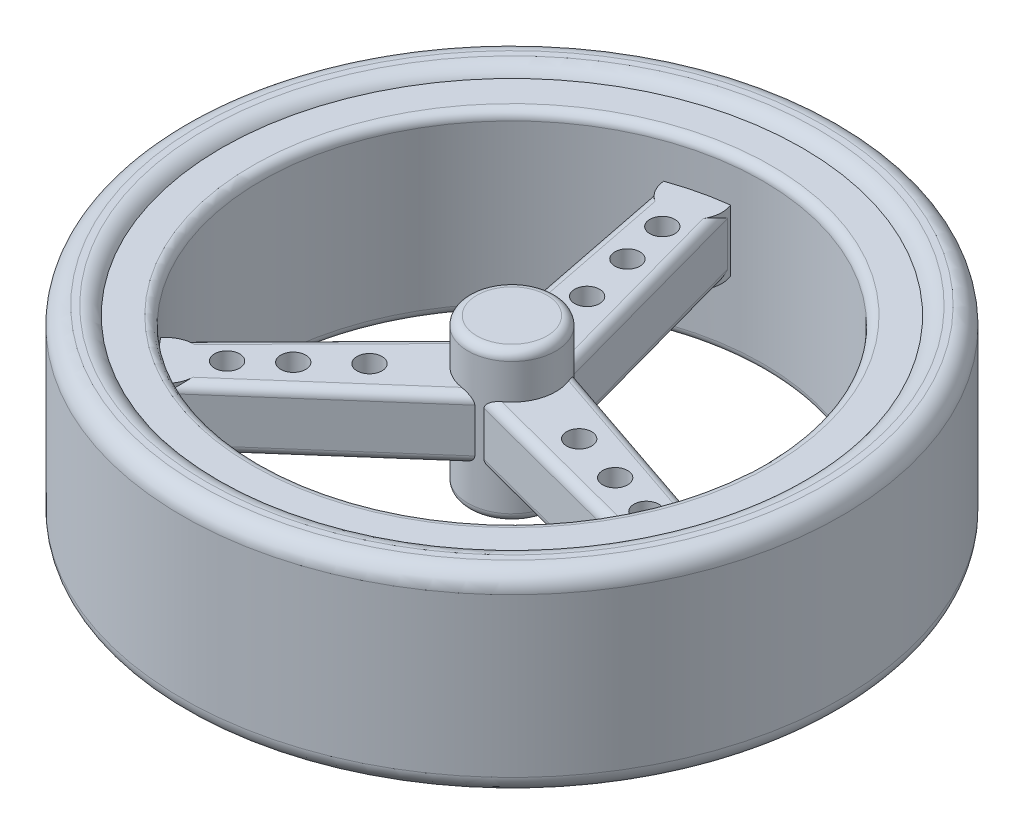
SolidWorks part; units mm, degrees
ref_plane "Front Plane" through (0, 0, 0) normal (0, 0, 1) x (1, 0, 0)
ref_plane "Top Plane" through (0, 0, 0) normal (0, 1, 0) x (1, 0, 0)
ref_plane "Right Plane" through (0, 0, 0) normal (1, 0, 0) x (0, 0, -1)
sketch "Sketch1" plane through (0, 0, 0) normal (0, 1, 0) x (1, 0, 0)
  circle A0 centre (0, 0) radius 5
  dimension "D1" = 10
extrude "Boss-Extrude1" add sketch "Sketch1" along normal blind 5
sketch "Sketch2" plane through (0, 5, 0) normal (0, 1, 0) x (1, 0, 0)
  line L0 (-3.2976, 27.8407) -> (3.3254, 3.7339)
  line L1 (0, 0) -> (0, 0.3854) construction
  line L2 (-1.1506, 4.8658) -> (-0.503, 2.1273) construction
  line L3 (-9.5211, 26.369) -> (-4.6455, 1.849)
  line L4 (27.5968, -4.939) -> (3.9241, 3.0986)
  line L5 (25.7595, -11.0646) -> (1.571, -4.7468)
  line L6 (-18.0757, -21.43) -> (0.7214, -4.9477)
  line L7 (-22.4619, -16.7761) -> (-4.8963, 1.0129)
  circle A0 centre (0, 0) radius 5 construction
  arc A1 (-4.6455, 1.849) -> (3.3254, 3.7339) centre (0, 0) cw
  arc A2 (-9.5211, 26.369) -> (-3.2976, 27.8407) centre (-6.4093, 27.1048) cw
  arc A3 (27.5968, -4.939) -> (25.7595, -11.0646) centre (26.6782, -8.0018) cw
  arc A4 (3.9241, 3.0986) -> (1.571, -4.7468) centre (0, 0) cw
  arc A5 (-18.0757, -21.43) -> (-22.4619, -16.7761) centre (-20.2688, -19.1031) cw
  arc A6 (0.7214, -4.9477) -> (-4.8963, 1.0129) centre (0, 0) cw
  point P24 (0, 0)
  dimension "D1" = 25
  dimension "D2" = 3
extrude "Boss-Extrude4" add sketch "Sketch2" along normal blind 7 separate body
sketch "Sketch3" plane through (0, 5, 0) normal (0, 1, 0) x (1, 0, 0)
  line L0 (-1.1506, 4.8658) -> (1.1506, -4.8658) construction
  arc A0 (3.3254, 3.7339) -> (-4.6455, 1.849) centre (0, 0) ccw construction
  circle A1 centre (0, 0) radius 5 construction
sketch "Sketch4" plane through (0, 5, 0) normal (0, 1, 0) x (1, 0, 0)
  circle A0 centre (0, 0) radius 5
  dimension "D1" = 10
extrude "Boss-Extrude5" add sketch "Sketch4" along normal blind 12
sketch "Sketch5" plane through (0, 17, 0) normal (0, 1, 0) x (1, 0, 0)
  circle A0 centre (0, 0) radius 28.5413
  circle A1 centre (0, 0) radius 33.0429
extrude "Boss-Extrude6" add sketch "Sketch5" against normal blind 20
fillet "Fillet1" radius 1 4 edges at (0, 17, 5) (0, 0, 5) (0, 17, 28.5413) (0, -3, 28.5413)
fillet "Fillet2" radius 1 10 edges at (-13.6791, 12, 7.8816) (-7.0833, 12, -14.109) (13.6652, 12, 7.9057) (15.7604, 12, 0.9202) (0.0139, 12, -15.7873) (0.0139, 5, -15.7873) (-7.0833, 5, -14.109) (-13.6791, 5, 7.8816) (-8.6771, 5, 13.1889) (13.6652, 5, 7.9057)
fillet "Fillet3" radius 1 1 edges at (-8.6771, 12, 13.1889)
sketch "Sketch9" plane through (0, -3, 0) normal (0, -1, 0) x (1, 0, 0)
  circle A0 centre (0, 0) radius 33.0429
  circle A1 centre (0, 0) radius 37.5
  dimension "D1" = 75
extrude "Boss-Extrude10" add sketch "Sketch9" against normal blind 21 and the other way blind 1
fillet "Fillet4" radius 2 2 edges at (0, -4, -33.0429) (0, 18, -33.0429)
fillet "Fillet5" radius 2 2 edges at (0, 18, -37.5) (0, -4, -37.5)
ref_plane "Plane1" through (0, 0, -37.5) normal (0, 0, -1) x (-1, 0, 0)
sketch "Sketch11" plane through (0, 0, -37.5) normal (0, 0, -1) x (-1, 0, 0)
  line L0 (2.1091, 14.5) -> (0, 14.5)
  line L1 (0, 16) -> (2.1091, 16)
  line L2 (0, 16) -> (0, -2)
  line L3 (0, -2) -> (2.1091, -2)
  line L4 (2.1091, 16) -> (2.1091, -2)
  line L5 (-37.5, 16) -> (37.5, 16) construction
  line L6 (37.5, -2) -> (-37.5, -2) construction
  line L7 (2.1091, 12.5) -> (0, 12.5)
  line L8 (2.1091, 10.5) -> (0, 10.5)
  line L9 (2.1091, 8.5) -> (0, 8.5)
  line L10 (2.1091, 6.5) -> (0, 6.5)
  line L11 (2.1091, 4.5) -> (0, 4.5)
  line L12 (2.1091, 2.5) -> (0, 2.5)
  line L13 (2.1091, 0.5) -> (0, 0.5)
  line L14 (2.1091, -1.5) -> (0, -1.5)
  dimension "D1" = 1.5
  dimension "D2" = 9
extrude "Boss-Extrude14" add sketch "Sketch11" along normal blind 0.2 separate body contours L4 L1 L2 L0 | L8 L4 L7 L2 | L10 L4 L9 L2 | L12 L4 L11 L2 | L14 L4 L13 L2 region at (-1.0545, 15.25, -37.5) region at (-1.0545, 11.5, -37.5) region at (-1.0545, 7.5, -37.5) region at (-1.0545, 3.5, -37.5) region at (-1.0545, -0.5, -37.5)
sketch "Sketch13" plane through (0, 0, 0) normal (0, -1, 0) x (1, 0, 0)
  circle A0 centre (0, 0) radius 1.75
  dimension "D1" = 3.5
extrude "Cut-Extrude2" cut sketch "Sketch13" against normal blind 7
sketch "Sketch14" plane through (0, 5, 0) normal (0, -1, 0) x (1, 0, 0)
  line L0 (0, 0) -> (-16.7288, 15.6837) construction
  circle A0 centre (-16.7288, 15.6837) radius 1.4215
  circle A1 centre (0, 0) radius 4 construction
  circle A2 centre (-12.8433, 12.0409) radius 1.4215
  circle A3 centre (-8.3644, 7.8419) radius 1.4215
  circle A4 centre (0, 0) radius 4 construction
  circle A5 centre (21.9469, 6.6457) radius 1.4215
  circle A6 centre (16.8494, 5.1021) radius 1.4215
  circle A7 centre (10.9734, 3.3228) radius 1.4215
  circle A8 centre (0, 0) radius 4 construction
  circle A9 centre (-5.2181, -22.3294) radius 1.4215
  circle A10 centre (-4.0061, -17.143) radius 1.4215
  circle A11 centre (-2.609, -11.1647) radius 1.4215
  point P25 (0, 0)
  dimension "D1" = 3
extrude "Cut-Extrude4" cut sketch "Sketch14" against normal blind 24
